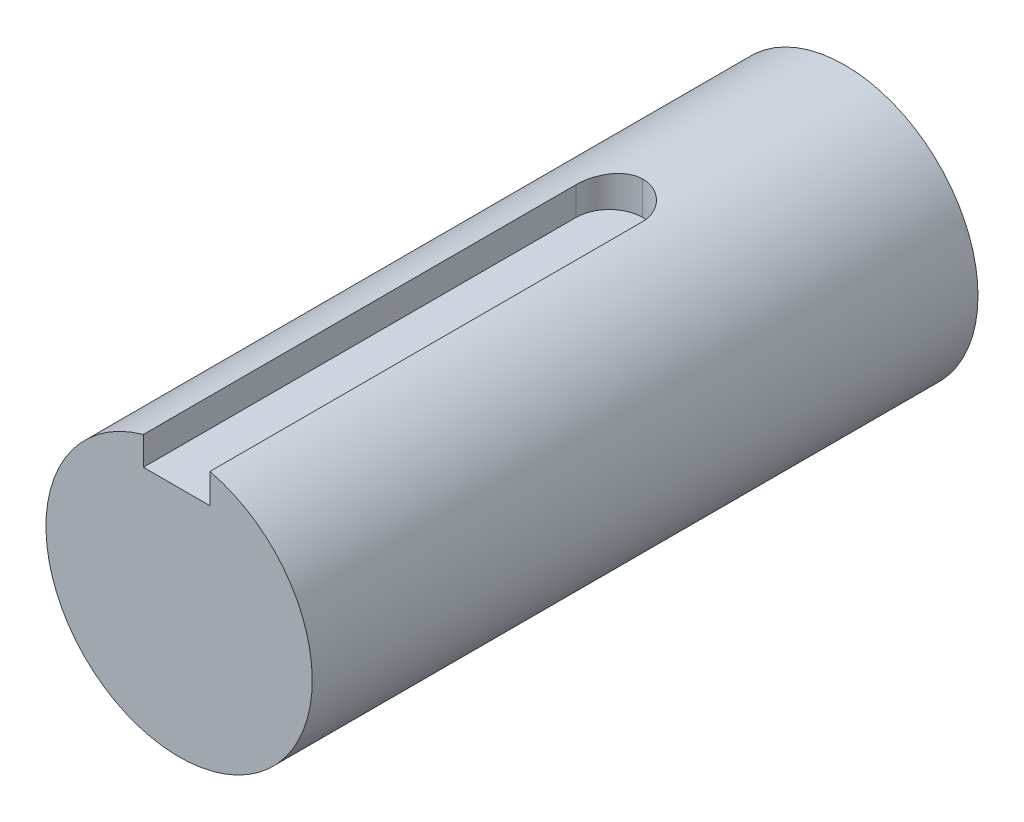
SolidWorks part; units mm, degrees
ref_plane "Front Plane" through (0, 0, 0) normal (0, 0, 1) x (1, 0, 0)
ref_plane "Top Plane" through (0, 0, 0) normal (0, 1, 0) x (1, 0, 0)
ref_plane "Right Plane" through (0, 0, 0) normal (1, 0, 0) x (0, 0, -1)
sketch "Sketch1" plane through (0, 0, 0) normal (0, 0, 1) x (1, 0, 0)
  circle A0 centre (0, 0) radius 50
extrude "Boss-Extrude1" add sketch "Sketch1" along normal blind 250
sketch "Sketch2" plane through (0, 0, 250) normal (0, 0, 1) x (1, 0, 0)
  line L1 (-13.4197, 37.4915) -> (11.5803, 37.4915)
  line L2 (-13.4197, 37.4915) -> (-13.4197, 62.4915)
  line L3 (-13.4197, 62.4915) -> (11.5803, 62.4915)
  line L4 (11.5803, 37.4915) -> (11.5803, 62.4915)
  line L5 (-13.4197, 37.4915) -> (11.5803, 62.4915) construction
  line L6 (-13.4197, 62.4915) -> (11.5803, 37.4915) construction
  circle A0 centre (0, 0) radius 50 construction
  point P0 (-0.9197, 49.9915)
extrude "Cut-Extrude1" cut sketch "Sketch2" against normal blind 175
fillet "Fillet1" radius 12.5 1 edges at (-13.4197, 42.8285, 75)
fillet "Fillet2" radius 12.5 1 edges at (11.5803, 43.066, 75)
